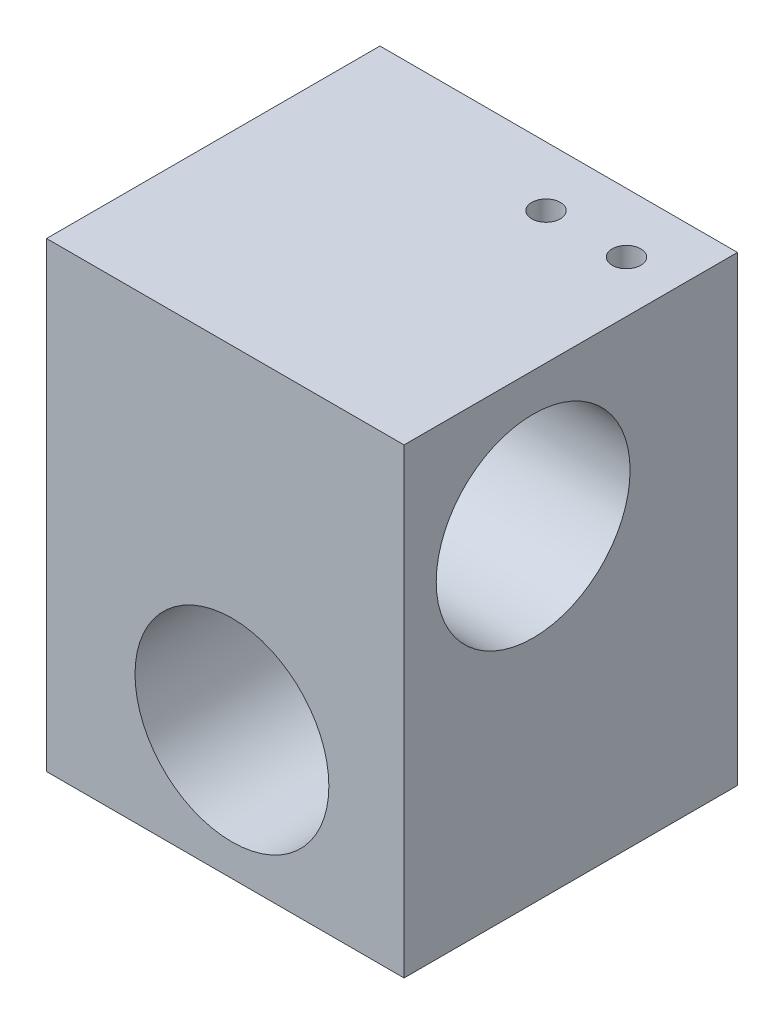
SolidWorks part; units mm, degrees
material "6061-T6 (SS)"
ref_plane "Front Plane" through (0, 0, 0) normal (0, 0, 1) x (1, 0, 0)
ref_plane "Top Plane" through (0, 0, 0) normal (0, 1, 0) x (1, 0, 0)
ref_plane "Right Plane" through (0, 0, 0) normal (1, 0, 0) x (0, 0, -1)
sketch "Sketch1" plane through (0, 0, 0) normal (0, 1, 0) x (1, 0, 0)
  line L1 (-10.9199, -8.1114) -> (14.4801, -8.1114)
  line L2 (-10.9199, -8.1114) -> (-10.9199, 17.2886)
  line L3 (-10.9199, 17.2886) -> (14.4801, 17.2886)
  line L4 (14.4801, -8.1114) -> (14.4801, 17.2886)
  dimension "D1" = 25.4
  dimension "D2" = 25.4
extrude "Boss-Extrude1" add sketch "Sketch1" along normal blind 28.7
sketch "Sketch2" plane through (0, 0, 8.1114) normal (0, 0, 1) x (1, 0, 0)
  line L2 (-10.9199, 0) -> (14.4801, 0) construction
  line L4 (1.7801, 28.7) -> (1.7801, 0) construction
  line L5 (-10.9199, 28.7) -> (14.4801, 28.7) construction
  circle A0 centre (3.7801, 8) radius 6.0254
  dimension "D1" = 8
  dimension "D3" = 12.0508
  dimension "D2" = 2
sketch "Sketch3" plane through (14.4801, 0, 0) normal (1, 0, 0) x (0, 0, -1)
  line L0 (4.5886, 28.7) -> (4.5886, 0) construction
  line L1 (-8.1114, 28.7) -> (17.2886, 28.7) construction
  line L2 (-8.1114, 0) -> (17.2886, 0) construction
  line L3 (-8.1114, 8) -> (17.2886, 8) construction
  line L4 (-8.1114, 14.0254) -> (-8.1114, 1.9746) construction
  line L5 (17.2886, 28.7) -> (17.2886, 0) construction
  circle A0 centre (4.5886, 20.319) radius 6.025
  dimension "D1" = 12.319
  dimension "D3" = 12.05
  dimension "D2" = 8
extrude "Cut-Extrude1" cut sketch "Sketch2" against normal through all
extrude "Cut-Extrude2" cut sketch "Sketch3" against normal through all
sketch "Sketch4" plane through (0, 28.7, 0) normal (0, 1, 0) x (1, 0, 0)
  line L0 (-10.9199, 13.5886) -> (14.4801, 13.5886) construction
  line L1 (3.0501, 17.2886) -> (3.0501, 25.4371) construction
  line L4 (-10.9199, 17.2886) -> (-10.9199, -8.1114) construction
  line L5 (14.4801, -8.1114) -> (14.4801, 17.2886) construction
  line L6 (1.7801, 17.2886) -> (1.7801, -8.1114) construction
  line L7 (-10.9199, -4.4114) -> (14.4801, -4.4114) construction
  line L9 (-10.9199, -8.1114) -> (14.4801, -8.1114) construction
  line L10 (11.2801, -8.1114) -> (11.2801, 17.2886) construction
  line L11 (14.4801, 17.2886) -> (-10.9199, 17.2886) construction
  line L12 (-10.5199, 4.5886) -> (14.4801, 4.5886) construction
  line L13 (6.2801, -8.1114) -> (6.2801, 17.2886) construction
  circle A0 centre (6.2801, 13.5886) radius 0.5412
  circle A1 centre (11.2801, 13.5886) radius 0.5782
  circle A2 centre (1.7801, -4.4114) radius 0.5921 construction
  dimension "D1" = 9.5
  dimension "D2" = 4.5
  dimension "D3" = 9
  dimension "D4" = 9
  dimension "D5" = 11.43
  dimension "D6" = 3.2
  dimension "D7" = 3.23
hole_wizard "#2-56 Tapped Hole1" positions "Sketch6" profile "Sketch5" tap size "#2-56" standard "ANSI Inch"
sketch "Sketch6" plane through (0, 28.7, 0) normal (0, 1, 0) x (1, 0, 0)
  point P0 (6.2801, 13.5886)
  point P3 (11.2801, 13.5886)
sketch "Sketch5" plane through (6.2801, 28.7, -13.5886) normal (1, 0, 0) x (0, 0, 1)
  line L0 (0, 0) -> (0, 7.189)
  line L1 (0, 7.189) -> (0.889, 6.6548)
  line L2 (0.889, 6.6548) -> (0.889, 0)
  line L5 (0.889, 0) -> (0, 0)
  line L10 (0, 7.189) -> (-0.889, 6.6548) construction
  line L11 (0, -6.35) -> (0, 107.95) construction
  dimension "Tap Drill Dia." = 1.778
  dimension "Tap Drill Depth" = 6.6548
  dimension "Drill Angle" = 118
cosmetic thread "Hole Thread3"
cosmetic thread "Hole Thread4"
sketch "Sketch7" plane through (0, 0, 0) normal (0, -1, 0) x (1, 0, 0)
  line L0 (1.7801, 8.1114) -> (1.7801, -17.2886) construction
  line L1 (-10.9199, 8.1114) -> (14.4801, 8.1114) construction
  line L2 (14.4801, -17.2886) -> (-10.9199, -17.2886) construction
  line L3 (-10.9199, -12.0886) -> (14.4801, -12.0886) construction
  line L4 (14.4801, 8.1114) -> (14.4801, -17.2886) construction
  line L5 (14.4801, -4.5886) -> (-10.9199, -4.5886) construction
  line L6 (-10.9199, -17.2886) -> (-10.9199, 8.1114) construction
  line L7 (11.7801, 8.1114) -> (11.7801, -17.2886) construction
  line L8 (-10.9199, 4.4114) -> (14.4801, 4.4114) construction
  line L9 (-4.2199, 8.1114) -> (-4.2199, -17.2886) construction
  circle A0 centre (11.7801, 4.4114) radius 0.4277 construction
  circle A1 centre (11.7801, -12.0886) radius 0.6504
  circle A2 centre (-4.2199, 4.4114) radius 0.6438 construction
  circle A3 centre (-4.2199, -12.0886) radius 0.4564
  dimension "D2" = 10
sketch "Sketch10" plane through (0, 28.7, 0) normal (0, 1, 0) x (1, 0, 0)
  line L0 (-7.7449, -3.4364) -> (14.4801, -3.4364)
  line L2 (14.4801, -8.1114) -> (14.4801, 17.2886) construction
  line L3 (-10.9199, -1.4364) -> (14.4801, -1.4364) construction
  line L4 (-10.9199, -8.1114) -> (14.4801, -8.1114) construction
  line L5 (-10.9199, 17.2886) -> (-10.9199, -8.1114)
  line L6 (-10.9199, -8.1114) -> (14.4801, -8.1114)
  line L7 (14.4801, -8.1114) -> (14.4801, -3.4364)
  line L9 (-10.9199, 17.2886) -> (-7.7449, 17.2886)
  line L12 (-7.7449, 17.2886) -> (-7.7449, -3.4364)
  dimension "D1" = 2
  dimension "D2" = 4.675
  dimension "D3" = 3.175
extrude "Cut-Extrude3" cut sketch "Sketch10" against normal through all
sketch "Sketch12" plane through (0, 0, 0) normal (0, -1, 0) x (1, 0, 0)
  line L0 (-2.2453, -17.2886) -> (-2.2453, 3.4364) construction
  line L1 (-7.7449, -10.6136) -> (-7.7449, 1.4364) construction
  line L2 (-7.7449, 1.4364) -> (14.4801, 1.4364) construction
  line L3 (9.8055, 3.4364) -> (9.8055, -17.2886) construction
  line L4 (-7.7449, -10.6136) -> (14.4801, -10.6136) construction
  line L5 (-2.2453, -17.2886) -> (-7.7449, -17.2886) construction
  line L6 (-3.9349, -13.5886) -> (-3.9349, -3.5886) construction
  line L7 (9.8055, -17.2886) -> (-2.2453, -17.2886) construction
  line L8 (3.7801, -17.2886) -> (3.7801, 6.2232) construction
  line L9 (14.4801, 1.4364) -> (14.4801, -10.6136) construction
  line L10 (14.4801, -4.5886) -> (-10.4587, -4.5886) construction
  circle A0 centre (-3.9349, -3.5886) radius 0.508
  circle A1 centre (-3.9349, -13.5886) radius 0.508
  dimension "D4" = 1.016
  dimension "D5" = 1.016
  dimension "D1" = 9
  dimension "D2" = 1
  dimension "D3" = 3.81
  dimension "D6" = 7.715
  dimension "D7" = 11.525
hole_wizard "#2-56 Tapped Hole2" positions "Sketch14" profile "Sketch15" tap size "#2-56" standard "ANSI Inch"
sketch "Sketch14" plane through (0, 0, 0) normal (0, -1, 0) x (-1, 0, 0)
  point P0 (3.9349, 13.5886)
  point P3 (3.9349, 3.5886)
sketch "Sketch15" plane through (-3.9349, 0, -13.5886) normal (1, 0, 0) x (0, 0, -1)
  line L0 (0, 0) -> (0, 7.189)
  line L1 (0, 7.189) -> (0.889, 6.6548)
  line L2 (0.889, 6.6548) -> (0.889, 0)
  line L5 (0.889, 0) -> (0, 0)
  line L10 (0, 7.189) -> (-0.889, 6.6548) construction
  line L11 (0, -6.35) -> (0, 107.95) construction
  dimension "Tap Drill Dia." = 1.778
  dimension "Tap Drill Depth" = 6.6548
  dimension "Drill Angle" = 118
cosmetic thread "Hole Thread5"
cosmetic thread "Hole Thread6"
sketch "Sketch16" [suppressed] plane through (0, 28.7, 0) normal (0, 1, 0) x (1, 0, 0)
  line L0 (-7.7449, -1.4364) -> (14.4801, 10.6136) construction
  line L1 (14.4801, 10.6136) -> (-7.7449, 10.6136) construction
  line L2 (-7.7449, 10.6136) -> (14.4801, -1.4364) construction
  line L3 (3.3676, 4.5886) -> (-12.3595, 4.5886) construction
  line L5 (14.4801, 17.2886) -> (-7.7449, 17.2886) construction
  dimension "D1" = 12.7
